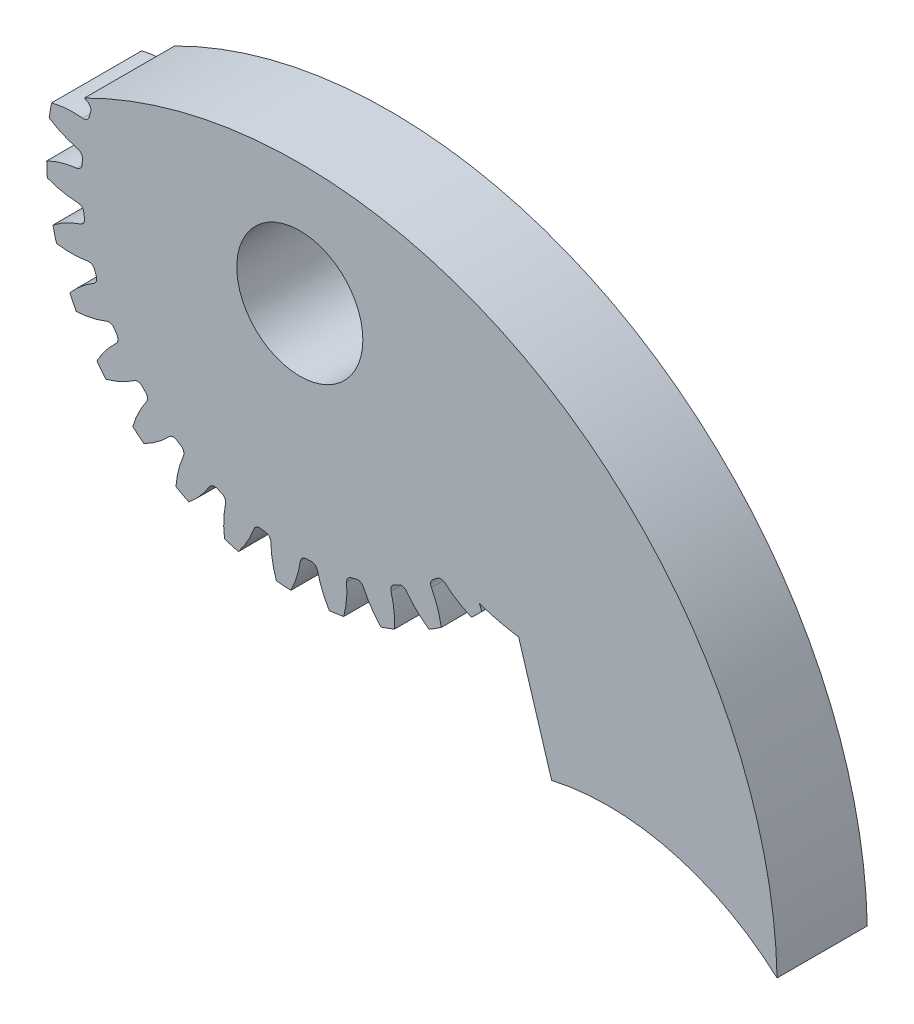
SolidWorks part; units mm, degrees
material "ABS"
ref_plane "Front" through (0, 0, 0) normal (0, 0, 1) x (1, 0, 0)
ref_plane "Top" through (0, 0, 0) normal (0, 1, 0) x (1, 0, 0)
ref_plane "Right" through (0, 0, 0) normal (1, 0, 0) x (0, 0, -1)
sketch "Sketch3" plane through (0, 0, 0) normal (0, 0, 1) x (1, 0, 0)
  circle A0 centre (0, 0) radius 40.64
  dimension "od" = 81.28
extrude "gearBody" add sketch "Sketch3" along normal blind 9.652
sketch "Sketch2" plane through (0, 0, 0) normal (0, 0, 1) x (1, 0, 0)
  line L0 (0, 0) -> (34.0786, 14.1158) construction
  line L1 (45.4751, -11.4855) -> (0, 0) construction
  line L2 (0, 0) -> (36.3143, 0) construction
  line L3 (38.0972, -0.458) -> (37.8451, -4.4001) construction
  line L5 (37.9712, -2.4291) -> (0, 0) construction
  line L7 (0, 0) -> (36.8864, 0) construction
  arc A0 (36.879, -0.7403) -> (36.6727, -3.9649) centre (0, 0) ccw construction
  arc A1 (40.637, 0.4947) -> (40.2427, -5.6687) centre (0, 0) ccw construction
  arc A2 (38.0972, -0.458) -> (37.8451, -4.4001) centre (0, 0) ccw construction
  arc A3 (34.9015, -2.6404) -> (34.9534, -1.8283) centre (0, 0) ccw
  arc A4 (45.4751, -11.4855) -> (35.6466, -3.6712) centre (32.0022, -18.3431) ccw
  arc A5 (45.4751, -11.4855) -> (46.5679, 5.5974) centre (0, 0) ccw
  arc A6 (46.5679, 5.5974) -> (35.8238, -0.9008) centre (34.0786, 14.1158) cw
  arc A7 (34.9534, -1.8283) -> (35.8238, -0.9008) centre (35.9376, -1.8798) cw
  arc A8 (35.6466, -3.6712) -> (34.9015, -2.6404) centre (35.8842, -2.7147) cw
  point P6 (46.5679, 5.5974)
  point P22 (45.4751, -11.4855)
  dimension "baseDia" = 73.7729
  dimension "od" = 81.28
  dimension "pd" = 76.2
  dimension "rd" = 70.0024
  dimension "rFillet" = 0.9855
  dimension "pointX" = 46.5679
  dimension "pointY" = 5.5974
  dimension "CTT" = 3.9421
  dimension "flankCenterAngle" = 22.5
extrude "toothCut" cut sketch "Sketch2" along normal through all
pattern_circular "CirPattern1" count 30 over 360 about axis through (0, 0, 9.652) along (0, 0, -1) of "toothCut"
scale "Scale1" scale about centroid uniform scaling no x scale factor 0.666667 y scale factor 0.666667 z scale factor 1
sketch "hub1Dia" plane through (0, 0, 0) normal (0, 0, -1) x (-1, 0, 0)
  circle A0 centre (0, 0) radius 12.7
  dimension "hub1Dia" = 25.4
sketch "hub2Dia" plane through (0, 0, 9.652) normal (0, 0, 1) x (1, 0, 0)
  circle A0 centre (0, 0) radius 12.7
  dimension "hub2dia" = 25.4
sketch "boreDia" plane through (0, 0, 0) normal (0, 0, 1) x (1, 0, 0)
  circle A0 centre (0, 0) radius 6.7469
  dimension "boreDia" = 13.4937
extrude "bore" cut sketch "boreDia" against normal mid plane 25400
sketch "Sketch4" plane through (0, 0, 9.652) normal (0, 0, 1) x (1, 0, 0)
  circle A0 centre (0, -38.1) radius 51.1048
  arc A2 (-27.9892, 4.6587) -> (27.9892, 4.6587) centre (0, 0) cw
  dimension "D1" = 102.2096
  dimension "D2" = 38.1
extrude "Cut-Extrude1" cut sketch "Sketch4" against normal through all contours A0 region at (0, 17.6405, 9.652)
sketch "Sketch5" plane through (0, 0, 9.652) normal (0, 0, 1) x (1, 0, 0)
  line L0 (0, -38.1) -> (51.1048, -38.1) construction
  line L1 (0, 0) -> (0, -38.1) construction
  line L2 (0, -38.1) -> (-25.5524, 6.1581) construction
  line L3 (0, -38.1) -> (44.2581, -63.6524) construction
  line L4 (23.4248, -19.2156) -> (26.9592, -30.742)
  circle A0 centre (0, -38.1) radius 51.1048 construction
  arc A1 (21.891, 8.0789) -> (-23.0664, 7.5031) centre (0, -38.1) ccw construction
  circle A2 centre (0, -38.1) radius 14.3933 construction
  circle A3 centre (32.9956, -57.15) radius 27.0891 construction
  arc A4 (26.9592, -30.742) -> (51.0928, -36.9929) centre (32.9956, -57.15) cw
  arc A5 (51.0928, -36.9929) -> (8.2583, 12.3331) centre (0, -38.1) ccw
  spline S0 degree 2 poles (8.2583, 12.3331) (3.9786, -16.3376) (23.4248, -19.2156) knots 0 0 0 1 1 1
  dimension "D2" = 28.7867
  dimension "D4" = 54.1782
  dimension "D1" = 120
  dimension "D3" = 120
  dimension "D5" = 38.1
extrude "Boss-Extrude1" add sketch "Sketch5" against normal up to surface (9.652 mm away) up to face at (6.7469, 0, 0)
equation "\"Aft_Section_Length\" = 32in"
equation "\"Mid_Coupler_Length\" = 12in"
equation "\"AB_Coupler_OD_Length\"= 1in"
equation "\"AB_Coupling_Section_Length\"= 0.375in"
equation "\"AB_Coupler_Length\"= \"AB_Coupler_OD_Length\" + \"AB_Coupling_Section_Length\" * 2"
equation "\"Cutout_Angle\" = 60"
equation "\"AB_Paddle_Height\" = 0.375in"
equation "\"AB_Coupler_Num_Screws\"= 4"
equation "\"Num_Cutouts\" = 4"
equation "\"AB_Coupler_OD\"= 4.024in"
equation "\"AB_Coupler_ID\"= 3.7in"
equation "\"AB_Coupler_Surface_Diameter\"= 3.899in"
equation "\"AB_Coupling_Screw_Diameter\"= 0.1065in"
equation "\"AB_Central_Bushing_Length\" = 0.75in"
equation "\"Lead_Screw_Dist\" = 2in"
equation "\"Lead_Screw_Diam\" = 0.375in"
equation "\"Lead_Screw_Length\" = \"Mid_Coupler_Length\" + 2*0.375in + 2*0.5in"
equation "\"Paddle_Pin_Offset\" = 0.25in"
equation "\"Paddle_Pin_Radius\" = 2.25*2/3in"
equation "\"Fwd_BKHD_From_Top\" = 18in"
equation "\"D1@Sketch4\" = \"Body_Tube_OD\""
equation "\"D2@Sketch4\"=\"Paddle_Pin_Radius\""
equation "\"Motor_OD\" = 54mm"
equation "\"Paddle_Gear_OD\" = 3.2in"
equation "\"Drive_Gear_OD\" = 1.7*2/3in"
equation "\"Fin_Thickness\" = 0.118in"
equation "\"DB9_Hole_Dist\" = 25mm"
equation "\"Motor_Length\" = 401mm"
equation "\"Body_Tube_OD\"= 4.024in"
equation "\"Body_Tube_ID\"= 3.90in"
equation "\"Coupler_OD\" = 3.899in"
equation "\"Coupler_ID\" = 3.755in"
equation "\"Fwd_Section_Length\" = 20in"
equation "\"Mid_Section_Length\" = 4in"
equation "\"Aft_Upper_Tube_Length\" = 10in"
equation "\"Aft_Lower_Tube_Length\" = 18in"
equation "\"Nosecone_Coupler_Length\" = 5in"
equation "\"Avionics_Bulkhead_Thickness\" = 0.25in"
equation "\"Avionics_Bulkhead_Lip\" = 0.125in"
equation "\"Avionics_Board_Length\" = \"Mid_Coupler_Length\" - 2*\"Avionics_Bulkhead_Lip\""
equation "\"Lead_Screw_Hole_Diam\" = 0.386in"
equation "\"Centering_Ring_Cutout_Dia\"=1.5in"
equation "\"Airbrakes_Wire_Hole_Dist\" = 1.1in"
equation "\"Airbrakes_Wire_Hole_Dia\" = 0.25in"
equation "\"DB9_Relief_Width\" = 0.47in"
equation "\"DB9_Relief_Hole_Offset\" = 0.09in"
equation "\"Servo_Gear_Offset\" = 0.5in"
equation "\"D2@Sketch5\"=\"Drive_Gear_OD\""
equation "\"D5@Sketch5\"=\"Paddle_Pin_Radius\""
